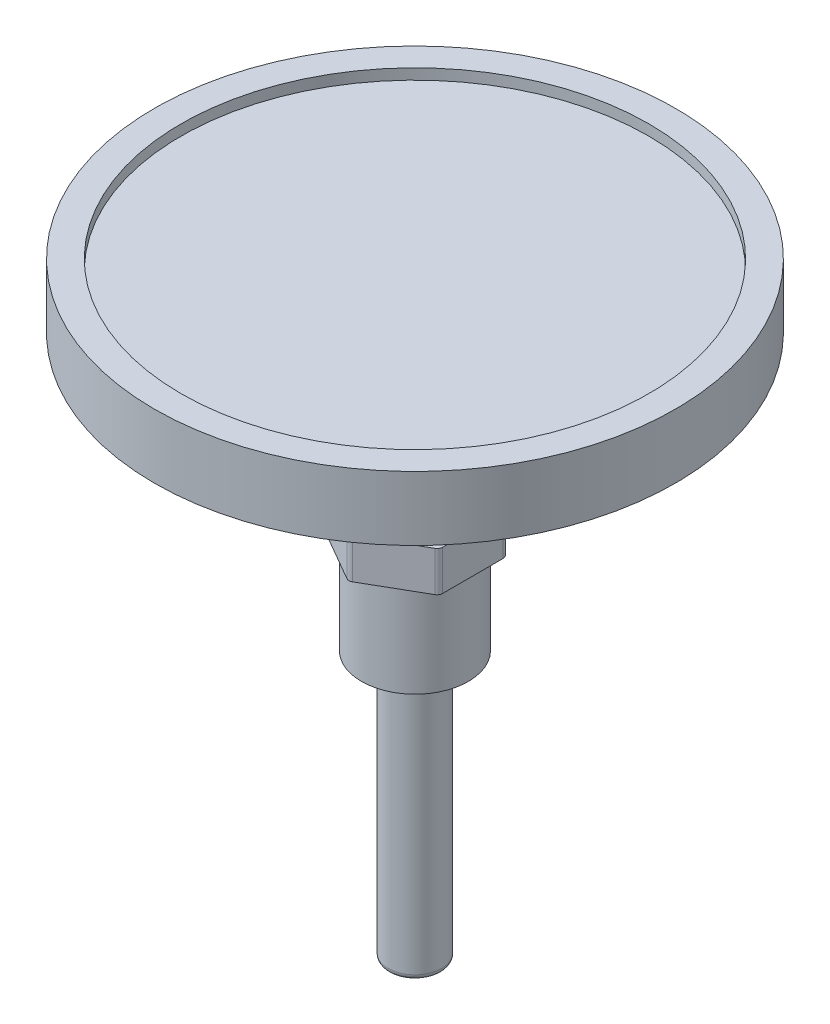
SolidWorks part; units mm, degrees
ref_plane "Front Plane" through (0, 0, 0) normal (0, 0, 1) x (1, 0, 0)
ref_plane "Top Plane" through (0, 0, 0) normal (0, 1, 0) x (1, 0, 0)
ref_plane "Right Plane" through (0, 0, 0) normal (1, 0, 0) x (0, 0, -1)
sketch "Sketch1" plane through (0, 0, 0) normal (0, 1, 0) x (1, 0, 0)
  circle A0 centre (0, 0) radius 5
  dimension "D1" = 10
extrude "Boss-Extrude1" add sketch "Sketch1" along normal blind 50
sketch "Sketch2" plane through (0, 50, 0) normal (0, 1, 0) x (1, 0, 0)
  circle A0 centre (0, 0) radius 10
  dimension "D1" = 20
extrude "Boss-Extrude2" add sketch "Sketch2" along normal blind 17.5
sketch "Sketch3" plane through (0, 67.5, 0) normal (0, 1, 0) x (1, 0, 0)
  line L0 (0, 0) -> (0, -12.5) construction
  line L1 (10.8253, -6.25) -> (10.8253, 6.25)
  line L2 (10.8253, 6.25) -> (0, 12.5)
  line L3 (0, 12.5) -> (-10.8253, 6.25)
  line L4 (-10.8253, 6.25) -> (-10.8253, -6.25)
  line L5 (-10.8253, -6.25) -> (0, -12.5)
  line L6 (0, -12.5) -> (10.8253, -6.25)
  circle A0 centre (0, 0) radius 10.8253 construction
  dimension "D1" = 12.5
extrude "Boss-Extrude3" add sketch "Sketch3" along normal blind 7.5
sketch "Sketch4" plane through (0, 75, 0) normal (0, 1, 0) x (1, 0, 0)
  circle A0 centre (0, 0) radius 8.5
  dimension "D1" = 17
extrude "Boss-Extrude4" add sketch "Sketch4" along normal blind 16.5
sketch "Sketch5" plane through (0, 91.5, 0) normal (0, 1, 0) x (1, 0, 0)
  circle A0 centre (0, 0) radius 20
  dimension "D1" = 40
extrude "Boss-Extrude5" add sketch "Sketch5" along normal blind 10
sketch "Sketch6" plane through (0, 101.5, 0) normal (0, 1, 0) x (1, 0, 0)
  circle A0 centre (0, 0) radius 48.75
  dimension "D1" = 97.5
extrude "Boss-Extrude6" add sketch "Sketch6" along normal blind 12
chamfer "Chamfer1" distance 10 angle 55 1 edges at (0, 101.5, 20) first distance on face at (0, 101.5, 20)
sketch "Sketch7" plane through (0, 113.5, 0) normal (0, 1, 0) x (1, 0, 0)
  circle A0 centre (0, 0) radius 43.75
  dimension "D1" = 87.5
extrude "Cut-Extrude2" cut sketch "Sketch7" against normal blind 2
fillet "Fillet1" radius 1 7 edges at (10.8253, 71.25, -6.25) (10.8253, 71.25, 6.25) (0, 71.25, 12.5) (-10.8253, 71.25, 6.25) (-10.8253, 71.25, -6.25) (0, 71.25, -12.5) (0, 0, 5)
